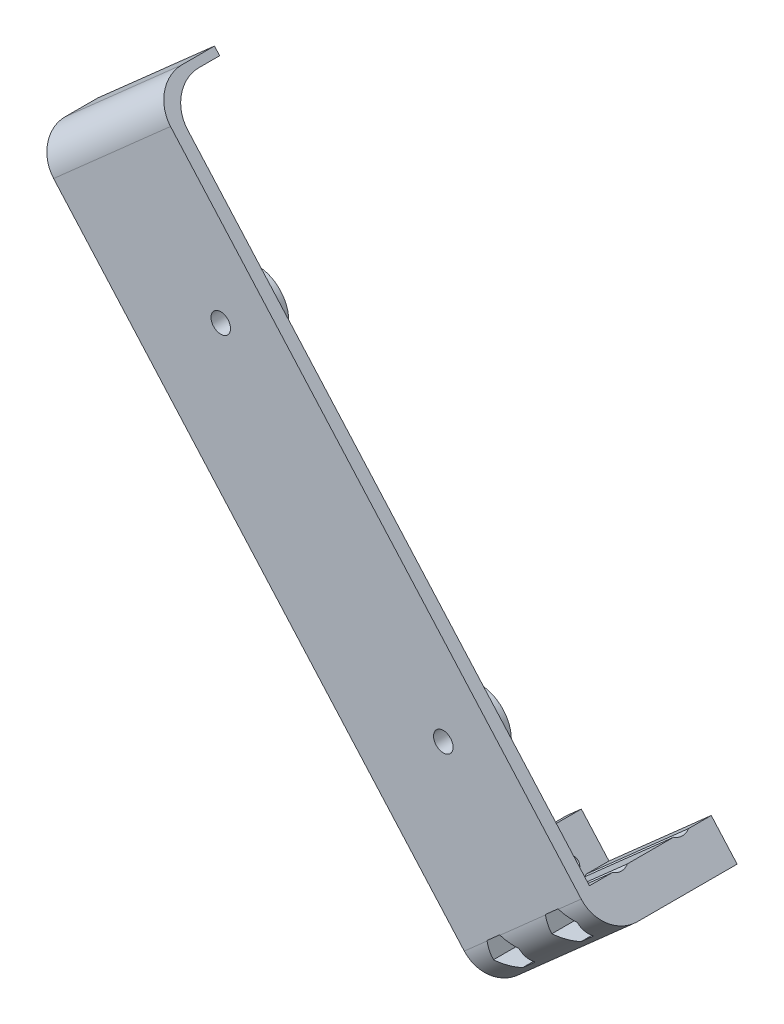
SolidWorks part; units mm, degrees
ref_plane "Front Plane" through (0, 0, 0) normal (0, 0, 1) x (1, 0, 0)
ref_plane "Top Plane" through (0, 0, 0) normal (0, 1, 0) x (1, 0, 0)
ref_plane "Right Plane" through (0, 0, 0) normal (1, 0, 0) x (0, 0, -1)
sketch "Sketch1" plane through (0, 0, 0) normal (0, 0, 1) x (1, 0, 0)
  circle A0 centre (0, 0) radius 10.2489
  circle A1 centre (-72.4111, 81.7658) radius 10.2489
extrude "Boss-Extrude1" add sketch "Sketch1" along normal up to surface (2.9845 mm away)
sketch "Sketch2" plane through (0, 0, 2.9845) normal (0, 0, 1) x (1, 0, 0)
  circle A0 centre (-72.4111, 81.7658) radius 10.2489
  circle A1 centre (0, 0) radius 10.2489
extrude "Boss-Extrude2" add sketch "Sketch2" along normal blind 5.08
sketch "Sketch3" plane through (0, 0, 8.0645) normal (0, 0, 1) x (1, 0, 0)
  line L0 (-134.0697, 103.5005) -> (-96.0391, 137.1801)
  line L1 (-134.0697, 103.5005) -> (14.1204, -63.8342)
  line L2 (-96.0391, 137.1801) -> (52.151, -30.1546)
  line L3 (14.1204, -63.8342) -> (52.151, -30.1546)
  line L4 (14.1204, -63.8342) -> (52.151, -30.1546) construction
  dimension "D1" = 0
extrude "Boss-Extrude3" add sketch "Sketch3" along normal blind 3.81
hole_wizard "1/4 (0.25) Diameter Hole1" positions "Sketch4" profile "Sketch5" hole size "1/4" standard "ANSI Inch" end condition through all
sketch "Sketch4" plane through (0, 0, 11.8745) normal (0, 0, 1) x (1, 0, 0)
  point P0 (0, 0)
  point P3 (-72.4111, 81.7658)
sketch "Sketch5" plane through (0, 0, 11.8745) normal (1, 0, 0) x (0, -1, 0)
  line L0 (0, 0) -> (0, 11.8745)
  line L1 (0, 11.8745) -> (3.175, 11.8745)
  line L2 (3.175, 11.8745) -> (3.175, 0)
  line L5 (3.175, 0) -> (0, 0)
  line L11 (0, -6.35) -> (0, 107.95) construction
  dimension "Thru Hole Dia." = 6.35
  dimension "Thru Hole Depth" = 11.8745
sketch "Sketch7" plane through (0, 0, 8.0645) normal (0, 0, -1) x (-1, 0, 0)
  line L0 (134.0697, 103.5005) -> (129.3159, 107.7104)
  line L1 (134.0697, 103.5005) -> (120.81, 88.5278)
  line L2 (129.3159, 107.7104) -> (116.0562, 92.7378)
  line L3 (120.81, 88.5278) -> (116.0562, 92.7378)
  line L4 (96.0391, 137.1801) -> (134.0697, 103.5005) construction
  line L5 (61.8507, 31.5295) -> (66.6045, 27.3195)
  line L6 (69.7345, 24.5476) -> (46.6379, 45.0017)
  line L7 (61.8507, 31.5295) -> (48.591, 16.5568)
  line L8 (66.6045, 27.3195) -> (53.3448, 12.3468)
  line L9 (48.591, 16.5568) -> (53.3448, 12.3468)
  line L10 (129.3159, 107.7104) -> (96.0391, 137.1801)
  line L11 (134.0697, 103.5005) -> (-14.1204, -63.8342)
  line M7 (-14.1204, -63.8342) -> (134.0697, 103.5005)
  line M8 (134.0697, 103.5005) -> (96.0391, 137.1801)
  dimension "D1" = 20
  dimension "D2" = 6.35
  dimension "D3" = 20
  dimension "D4" = 0
  dimension "D5" = 101.76
  dimension "D6" = 0
  dimension "D7" = 6.35
extrude "Boss-Extrude4" add sketch "Sketch7" along normal blind 17.78 contours L7 L9 L5 M7 | L3 L2 M7 M8 region at (-125.063, 98.1191, 8.0645) region at (-57.5977, 21.9381, 8.0645)
sketch "Sketch8" plane through (-19.0153, -16.8398, 0) normal (0.7486, 0.663, 0) x (0, 0, -1)
  circle A0 centre (0.8255, 54.61) radius 2.25
  circle A1 centre (0.8255, 156.37) radius 2.25
extrude "Cut-Extrude1" cut sketch "Sketch8" against normal blind 17.78
sketch "Sketch9" plane through (-19.0153, -16.8398, 0) normal (0.7486, 0.663, 0) x (0, 0, -1)
  line L0 (9.7155, 64.61) -> (-8.0645, 64.61)
  line L1 (9.7155, 64.61) -> (9.7155, 62.07)
  line L2 (-8.0645, 64.61) -> (-8.0645, 62.07)
  line L3 (9.7155, 62.07) -> (-8.0645, 62.07)
  line L4 (-8.0645, 44.61) -> (9.7155, 44.61)
  line L5 (-8.0645, 44.61) -> (-8.0645, 47.15)
  line L6 (9.7155, 44.61) -> (9.7155, 47.15)
  line L7 (-8.0645, 47.15) -> (9.7155, 47.15)
  line L8 (-8.0645, 166.37) -> (9.7155, 166.37)
  line L9 (-8.0645, 166.37) -> (-8.0645, 163.83)
  line L10 (9.7155, 166.37) -> (9.7155, 163.83)
  line L11 (-8.0645, 163.83) -> (9.7155, 163.83)
  line L12 (9.7155, 146.37) -> (-8.0645, 146.37)
  line L13 (9.7155, 146.37) -> (9.7155, 148.91)
  line L14 (-8.0645, 146.37) -> (-8.0645, 148.91)
  line L15 (9.7155, 148.91) -> (-8.0645, 148.91)
  dimension "D1" = 2.54
extrude "Boss-Extrude5" add sketch "Sketch9" along normal blind 17.78
sketch "Sketch10" plane through (-110.3006, 124.5502, 0) normal (-0.663, 0.7486, 0) x (0.7486, 0.663, 0)
  line L0 (-7.62, 9.7155) -> (-7.62, -8.0645)
  line L1 (-7.62, 9.7155) -> (-25.4, 9.7155)
  line L4 (-25.4, 9.7155) -> (-7.62, -8.0645)
extrude "Cut-Extrude2" cut sketch "Sketch10" against normal up to surface (20 mm away) up to face at (-111.7778, 96.5267, -0.8255)
sketch "Sketch11" plane through (-42.8354, 48.3692, 0) normal (-0.663, 0.7486, 0) x (0.7486, 0.663, 0)
  line L0 (-7.62, 9.7155) -> (-7.62, -8.0645)
  line L1 (-7.62, 9.7155) -> (-25.4, 9.7155)
  line L4 (-25.4, 9.7155) -> (-7.62, -8.0645)
  dimension "D1" = 17.78
extrude "Cut-Extrude3" cut sketch "Sketch11" against normal up to surface (20 mm away) up to face at (-44.3126, 20.3457, -0.8255)
sketch "Sketch13" plane through (-110.3006, 124.5502, 0) normal (-0.663, 0.7486, 0) x (0.7486, 0.663, 0)
  line L0 (-25.4, 9.7155) -> (19.05, 9.7155)
  line L1 (19.05, -8.0645) -> (19.05, 9.7155)
  line L2 (19.05, -8.0645) -> (-7.62, -8.0645)
  line L3 (-7.62, -8.0645) -> (-25.4, 9.7155)
extrude "Boss-Extrude6" add sketch "Sketch13" against normal up to surface (2.54 mm away) up to face at (-123.195, 109.7382, 2.1378)
sketch "Sketch14" plane through (0, 0, 8.0645) normal (0, 0, -1) x (-1, 0, 0)
  line L0 (-52.151, -30.1546) -> (-14.1204, -63.8342)
  line L1 (-52.151, -30.1546) -> (-43.7311, -20.6469)
  line L2 (-14.1204, -63.8342) -> (-5.7005, -54.3265)
  line L3 (-43.7311, -20.6469) -> (-5.7005, -54.3265)
  dimension "D1" = 12.7
extrude "Boss-Extrude7" add sketch "Sketch14" along normal blind 39.624
sketch "Sketch15" plane through (0, 0, 11.8745) normal (0, 0, 1) x (1, 0, 0)
  line L0 (52.151, -30.1546) -> (14.1204, -63.8342)
  line L1 (52.151, -30.1546) -> (43.7311, -20.6469)
  line L2 (14.1204, -63.8342) -> (5.7005, -54.3265)
  line L3 (43.7311, -20.6469) -> (5.7005, -54.3265)
  line L4 (9.9104, -59.0803) -> (47.941, -25.4008)
  line L5 (28.9257, -42.2405) -> (24.7158, -37.4867)
  line L6 (24.7158, -37.4867) -> (52.151, -30.1546)
  line L7 (14.1204, -63.8342) -> (24.7158, -37.4867)
  line L9 (15.3012, -54.3064) -> (20.5171, -56.0488)
  line L10 (20.5171, -56.0488) -> (24.634, -52.4029)
  line L11 (24.634, -52.4029) -> (23.535, -47.0145)
  line L12 (23.535, -47.0145) -> (18.3191, -45.2721)
  line L13 (18.3191, -45.2721) -> (14.2022, -48.918)
  line L14 (14.2022, -48.918) -> (15.3012, -54.3064)
  line L15 (42.5503, -30.1747) -> (37.3344, -28.4323)
  line L16 (37.3344, -28.4323) -> (33.2175, -32.0782)
  line L17 (33.2175, -32.0782) -> (34.3165, -37.4666)
  line L18 (34.3165, -37.4666) -> (39.5324, -39.209)
  line L19 (39.5324, -39.209) -> (43.6493, -35.5631)
  line L20 (43.6493, -35.5631) -> (42.5503, -30.1747)
  circle A0 centre (19.4181, -50.6604) radius 4.7625 construction
  circle A1 centre (38.4334, -33.8207) radius 4.7625 construction
  dimension "D1" = 12.7
  dimension "D2" = 9.525
  dimension "D3" = 9.525
extrude "Cut-Extrude5" cut sketch "Sketch15" against normal blind 6.35 contours L16 L17 L6 L4 L15 | L19 L20 L6 L4 L18 | L6 L20 L4 | L6 L17 L4 | L4 L12 L7 | L4 L9 L7 | L13 L14 L4 L7 L12 | L10 L11 L4 L7 L9 region at (39.5724, -35.9689, 11.8745) region at (41.3421, -32.1947, 11.8745) region at (17.4524, -53.3513, 11.8745) region at (21.4129, -52.0508, 11.8745) region at (37.2944, -31.6724, 11.8745) region at (35.5246, -35.4466, 11.8745) region at (17.4233, -49.27, 11.8745) region at (21.3838, -47.9696, 11.8745)
sketch "Sketch16" plane through (0, 0, 5.5245) normal (0, 0, 1) x (1, 0, 0)
  point P7 (38.4334, -33.8207)
  point P13 (19.4181, -50.6604)
hole_wizard "#6 Clearance Hole1" positions "Sketch17" profile "Sketch18" hole size "#6" standard "ANSI Inch" end condition through all
sketch "Sketch17" plane through (0, 0, 5.5245) normal (0, 0, 1) x (1, 0, 0)
  point P0 (19.4181, -50.6604)
  point P3 (38.4334, -33.8207)
sketch "Sketch18" plane through (19.4181, -50.6604, 5.5245) normal (1, 0, 0) x (0, -1, 0)
  line L0 (0, 0) -> (0, 37.084)
  line L1 (0, 37.084) -> (1.8986, 37.084)
  line L2 (1.8986, 37.084) -> (1.8986, 0)
  line L5 (1.8986, 0) -> (0, 0)
  line L11 (0, -6.35) -> (0, 107.95) construction
  dimension "Thru Hole Dia." = 3.7973
  dimension "Thru Hole Depth" = 37.084
sketch "Sketch19" plane through (-23.7691, -21.0497, 0) normal (-0.7486, -0.663, 0) x (0, 0, 1)
  line L0 (8.0645, -44.45) -> (-31.5595, -44.45)
  line L1 (8.0645, -44.45) -> (8.0645, -30.8895)
  line L2 (-31.5595, -44.45) -> (-31.5595, -30.8895)
  line L3 (8.0645, -30.8895) -> (-31.5595, -30.8895)
extrude "Boss-Extrude8" add sketch "Sketch19" against normal blind 6.35
sketch "Sketch20" plane through (-19.0153, -16.8398, 0) normal (0.7486, 0.663, 0) x (0, 0, -1)
  line L0 (-8.0645, -30.8895) -> (-8.0645, -50.8895)
  line L1 (-8.0645, -30.8895) -> (31.6589, -30.8895)
  line L2 (-8.0645, -50.8895) -> (31.6589, -50.8895)
  line L3 (31.6589, -30.8895) -> (31.6589, -50.8895)
  line L4 (-8.0645, -44.45) -> (-8.0645, -30.8895) construction
  line L6 (11.7972, -30.8895) -> (11.7972, -50.8895)
  line L7 (11.7972, -40.8895) -> (-8.0645, -40.8895)
  line L8 (11.7972, -40.8895) -> (31.6589, -40.8895)
  circle A2 centre (21.728, -40.8895) radius 4.308
  circle A3 centre (1.8663, -40.8895) radius 4.308
  point P12 (1.8663, -40.8895)
  point P13 (21.728, -40.8895)
  line M6 (-8.0645, -44.45) -> (31.5595, -44.45)
  dimension "D1" = 20
hole_wizard "M4 Clearance Hole1" positions "Sketch21" profile "Sketch22" hole size "M4" standard "ANSI Metric" end condition through all
sketch "Sketch21" plane through (-19.0153, -16.8398, 0) normal (0.7486, 0.663, 0) x (0, 0, -1)
  point P0 (1.8663, -40.8895)
  point P3 (21.728, -40.8895)
sketch "Sketch22" plane through (8.0938, -47.4511, -1.8663) normal (0, 0, 1) x (-0.663, 0.7486, 0)
  line L0 (0, 0) -> (0, 117.2901)
  line L1 (0, 117.2901) -> (2.25, 117.2901)
  line L2 (2.25, 117.2901) -> (2.25, 0)
  line L5 (2.25, 0) -> (0, 0)
  line L11 (0, -6.35) -> (0, 107.95) construction
  dimension "Thru Hole Dia." = 4.5
  dimension "Thru Hole Depth" = 117.2901
extrude "Cut-Extrude6" cut sketch "Sketch20" along normal through all contours A3 L7 M6 | L7 A3 M6 | A3 M6 | A2 M6 region at (9.1816, -48.6794, -1.8663) region at (10.6541, -50.3422, -1.8663) region at (10.6541, -50.3422, -21.728)
fillet "Fillet1" radius 11 3 edges at (-110.9935, 120.5437, 8.0645) (-115.0544, 120.3403, 11.8745) (33.1357, -46.9944, 11.8745)
sketch "Sketch23" plane through (0, 0, 5.5245) normal (0, 0, 1) x (1, 0, 0)
  line L0 (37.3344, -28.4323) -> (33.2175, -32.0782) construction
  line L1 (33.2175, -32.0782) -> (34.3165, -37.4666) construction
  line L2 (34.3165, -37.4666) -> (39.5324, -39.209) construction
  line L3 (39.5324, -39.209) -> (43.6493, -35.5631) construction
  line L4 (43.6493, -35.5631) -> (42.5503, -30.1747) construction
  line L5 (42.5503, -30.1747) -> (37.3344, -28.4323) construction
  line L6 (14.2022, -48.918) -> (15.3012, -54.3064) construction
  line L7 (15.3012, -54.3064) -> (20.5171, -56.0488) construction
  line L8 (20.5171, -56.0488) -> (24.634, -52.4029) construction
  line L9 (24.634, -52.4029) -> (23.535, -47.0145) construction
  line L10 (23.535, -47.0145) -> (18.3191, -45.2721) construction
  line L11 (18.3191, -45.2721) -> (14.2022, -48.918) construction
  line L12 (37.3344, -28.4323) -> (33.2175, -32.0782)
  line L13 (33.2175, -32.0782) -> (34.3165, -37.4666)
  line L14 (34.3165, -37.4666) -> (39.5324, -39.209)
  line L15 (39.5324, -39.209) -> (43.6493, -35.5631)
  line L16 (43.6493, -35.5631) -> (42.5503, -30.1747)
  line L17 (42.5503, -30.1747) -> (37.3344, -28.4323)
  line L18 (14.2022, -48.918) -> (15.3012, -54.3064)
  line L19 (15.3012, -54.3064) -> (20.5171, -56.0488)
  line L20 (20.5171, -56.0488) -> (24.634, -52.4029)
  line L21 (24.634, -52.4029) -> (23.535, -47.0145)
  line L22 (23.535, -47.0145) -> (18.3191, -45.2721)
  line L23 (18.3191, -45.2721) -> (14.2022, -48.918)
extrude "Cut-Extrude7" cut sketch "Sketch23" against normal blind 6.35
sketch "Sketch24" plane through (0, 0, -9.7155) normal (0, 0, -1) x (-1, 0, 0)
  line L7 (117.7402, 94.6393) -> (116.0562, 92.7378)
  line L8 (116.0562, 92.7378) -> (120.81, 88.5278)
  line L9 (120.81, 88.5278) -> (134.0697, 103.5005)
  line L10 (134.0697, 103.5005) -> (96.0391, 137.1801)
  line L11 (96.0391, 137.1801) -> (94.3551, 135.2785)
  line L12 (94.3551, 135.2785) -> (127.6319, 105.8089)
  line L13 (127.6319, 105.8089) -> (117.7402, 94.6393)
  line L14 (117.7402, 94.6393) -> (116.0562, 92.7378)
  line L15 (116.0562, 92.7378) -> (120.81, 88.5278)
  line L16 (120.81, 88.5278) -> (134.0697, 103.5005)
  line L17 (134.0697, 103.5005) -> (96.0391, 137.1801)
  line L18 (96.0391, 137.1801) -> (94.3551, 135.2785)
  line L19 (94.3551, 135.2785) -> (127.6319, 105.8089)
  line L20 (127.6319, 105.8089) -> (117.7402, 94.6393)
  dimension "D1" = 0
